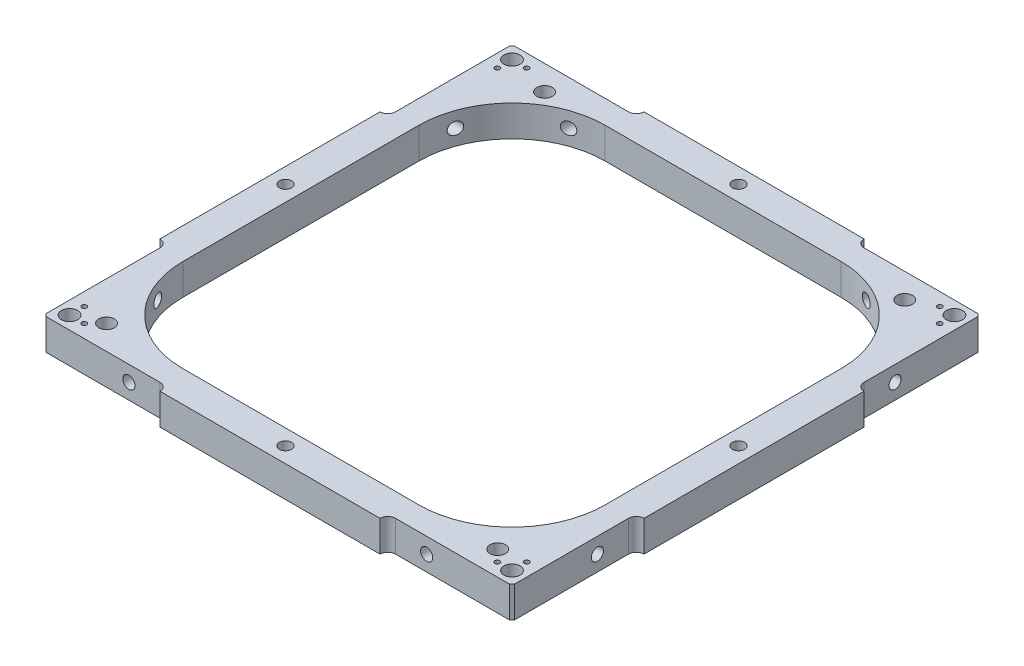
SolidWorks part; units mm, degrees
material "6061-T6 (SS)"
ref_plane "Front Plane" through (0, 0, 0) normal (0, 0, 1) x (1, 0, 0)
ref_plane "Top Plane" through (0, 0, 0) normal (0, 1, 0) x (1, 0, 0)
ref_plane "Right Plane" through (0, 0, 0) normal (1, 0, 0) x (0, 0, -1)
sketch "Sketch1" plane through (0, 0, 0) normal (0, 1, 0) x (1, 0, 0)
  line L0 (-49.5, 22.5125) -> (-47.9125, 22.5125)
  line L1 (-49.5, -49.5) -> (49.5, -49.5)
  line L2 (-49.5, -49.5) -> (-49.5, 49.5)
  line L3 (-49.5, 49.5) -> (49.5, 49.5)
  line L4 (49.5, -49.5) -> (49.5, 49.5)
  line L5 (-49.5, -49.5) -> (49.5, 49.5) construction
  line L6 (-49.5, 49.5) -> (49.5, -49.5) construction
  line L7 (-47.9125, 22.5125) -> (-47.9125, 47.9125)
  line L8 (-47.9125, 47.9125) -> (-22.5125, 47.9125)
  line L9 (-22.5125, 47.9125) -> (-22.5125, 49.5)
  line L10 (22.5125, 49.5) -> (22.5125, 47.9125)
  line L11 (22.5125, 47.9125) -> (47.9125, 47.9125)
  line L12 (47.9125, 47.9125) -> (47.9125, 22.5125)
  line L13 (47.9125, 22.5125) -> (49.5, 22.5125)
  line L14 (49.5, -22.5125) -> (47.9125, -22.5125)
  line L15 (47.9125, -22.5125) -> (47.9125, -47.9125)
  line L16 (47.9125, -47.9125) -> (22.5125, -47.9125)
  line L17 (22.5125, -47.9125) -> (22.5125, -49.5)
  line L18 (-22.5125, -49.5) -> (-22.5125, -47.9125)
  line L19 (-22.5125, -47.9125) -> (-47.9125, -47.9125)
  line L20 (-47.9125, -47.9125) -> (-47.9125, -22.5125)
  line L21 (-47.9125, -22.5125) -> (-49.5, -22.5125)
  point P0 (0, 0)
  dimension "D1" = 99
  dimension "D2" = 99
  dimension "D3" = 26.9875
  dimension "D4" = 1.5875
  dimension "D5" = 26.9875
  dimension "D6" = 1.5875
extrude "Boss-Extrude1" add sketch "Sketch1" along normal blind 6.35 contours L21 L20 L19 L18 L1 L17 L16 L15 L14 L4 L13 L12 L11 L10 L3 L9 L8 L7 L0 L2 region at (0, 0, 0)
chamfer "Chamfer1" distance 0.508 angle 45 4 edges at (47.9125, 3.175, -47.9125) (-47.9125, 3.175, -47.9125) (-47.9125, 3.175, 47.9125) (47.9125, 3.175, 47.9125)
fillet "Fillet1" radius 1.5875 8 edges at (-47.9125, 3.175, -22.5125) (-22.5125, 3.175, -47.9125) (22.5125, 3.175, -47.9125) (47.9125, 3.175, -22.5125) (47.9125, 3.175, 22.5125) (22.5125, 3.175, 47.9125) (-22.5125, 3.175, 47.9125) (-47.9125, 3.175, 22.5125)
hole_wizard "M4x0.7 Tapped Hole2" positions "Sketch2" profile "Sketch3" tap size "M4x0.7" standard "ANSI Metric" end condition through all
sketch "Sketch2" plane through (0, 0, 0) normal (0, -1, 0) x (-1, 0, 0)
  line L0 (-49.5, -22.5125) -> (-49.5, 22.5125) construction
  line L1 (22.5125, 49.5) -> (-22.5125, 49.5) construction
  line L5 (49.5, -22.5125) -> (49.5, 22.5125) construction
  line L6 (22.5125, -49.5) -> (-22.5125, -49.5) construction
  point P0 (-45.25, 45.25)
  point P2 (45.25, 45.25)
  point P4 (45.25, -45.25)
  point P6 (-45.25, -45.25)
  dimension "D1" = 4.25
  dimension "D2" = 4.25
  dimension "D3" = 4.25
  dimension "D4" = 4.25
  dimension "D5" = 4.25
  dimension "D6" = 4.25
  dimension "D7" = 4.25
  dimension "D8" = 4.25
sketch "Sketch3" plane through (45.25, 0, -45.25) normal (1, 0, 0) x (0, 0, -1)
  line L0 (0, 0) -> (0, 6.35)
  line L1 (0, 6.35) -> (1.65, 6.35)
  line L2 (1.65, 6.35) -> (1.65, 0)
  line L5 (1.65, 0) -> (0, 0)
  line L11 (0, -6.35) -> (0, 107.95) construction
  dimension "Thru Tap Drill Dia." = 3.3
  dimension "Thru Tap Drill Depth" = 6.35
cosmetic thread "Hole Thread6" parameters "D2"=4
cosmetic thread "Hole Thread7" parameters "D2"=4
cosmetic thread "Hole Thread8" parameters "D2"=4
cosmetic thread "Hole Thread9" parameters "D2"=4
hole_wizard "M3x0.5 Tapped Hole1" positions "Sketch6" profile "Sketch7" tap size "M3x0.5" standard "ANSI Metric"
sketch "Sketch6" plane through (0, 0, 47.9125) normal (0, 0, 1) x (1, 0, 0)
  line L1 (-24.1, 0) -> (-47.4045, 0) construction
  line L4 (47.4045, 0) -> (24.1, 0) construction
  line L5 (-24.1, 0) -> (-24.1, 6.35) construction
  line L7 (24.1, 6.35) -> (24.1, 0) construction
  point P0 (-30.45, 3.175)
  point P2 (30.45, 3.175)
  dimension "D1" = 6.35
  dimension "D2" = 3.175
  dimension "D3" = 6.35
  dimension "D4" = 3.175
sketch "Sketch7" plane through (-30.45, 3.175, 47.9125) normal (1, 0, 0) x (0, -1, 0)
  line L0 (0, 0) -> (0, 8.3711)
  line L1 (0, 8.3711) -> (1.25, 7.62)
  line L2 (1.25, 7.62) -> (1.25, 0)
  line L5 (1.25, 0) -> (0, 0)
  line L10 (0, 8.3711) -> (-1.25, 7.62) construction
  line L11 (0, -6.35) -> (0, 107.95) construction
  dimension "Tap Drill Dia." = 2.5
  dimension "Tap Drill Depth" = 7.62
  dimension "Drill Angle" = 118
cosmetic thread "Hole Thread1" parameters "D1"=4.7625, "D2"=3
cosmetic thread "Hole Thread2" parameters "D1"=4.7625, "D2"=3
ref_plane "Plane1" through (0, 0, 0) normal (0, 0, 1) x (1, 0, 0)
ref_plane "Plane2" through (0, 0, 0) normal (-1, 0, 0) x (0, 0, 1)
ref_axis "Axis1" through (0, -0.3175, 0) along (0, 1, 0)
pattern_circular "CirPattern1" count 4 over 360 about axis through (0, -0.3175, 0) along (0, 1, 0) of "M3x0.5 Tapped Hole1"
sketch "Sketch9" plane through (0, 6.35, 0) normal (0, 1, 0) x (1, 0, 0)
  line L0 (0, 3.4925) -> (0, -3.4925) construction
  line L1 (-3.4925, 0) -> (3.4925, 0) construction
  circle A0 centre (-40.005, -42.926) radius 1.5875
  circle A1 centre (40.005, -42.926) radius 1.5875
  circle A2 centre (37.465, 42.8625) radius 1.5875
  circle A3 centre (-36.195, 42.8625) radius 1.5875
  dimension "D7" = 3.175
  dimension "D4" = 73.66
  dimension "D1" = 40.005
  dimension "D2" = 40.005
  dimension "D3" = 2.54
  dimension "D5" = 42.8625
  dimension "D6" = 42.926
extrude "Cut-Extrude2" cut sketch "Sketch9" against normal through all
sketch "Sketch11" plane through (0, 6.35, 0) normal (0, 1, 0) x (1, 0, 0)
  line L0 (-22.5125, 49.5) -> (22.5125, 49.5) construction
  line L1 (-43.15, -43.15) -> (43.15, -43.15)
  line L2 (-43.15, -43.15) -> (-43.15, 43.15)
  line L3 (-43.15, 43.15) -> (43.15, 43.15)
  line L4 (43.15, -43.15) -> (43.15, 43.15)
  line L5 (-43.15, -43.15) -> (43.15, 43.15) construction
  line L6 (-43.15, 43.15) -> (43.15, -43.15) construction
  line L7 (49.5, -22.5125) -> (49.5, 22.5125) construction
  line L8 (-44.2725, 42.0275) -> (42.0275, -44.2725)
  line L9 (-42.0275, -44.2725) -> (44.2725, 42.0275)
  line L10 (-42.0275, 44.2725) -> (44.2725, -42.0275)
  line L11 (-44.2725, -42.0275) -> (42.0275, 44.2725)
  circle A5 centre (-36.195, 42.8625) radius 4.7625
  circle A6 centre (-36.195, 42.8625) radius 4.7625
  circle A9 centre (37.465, 42.8625) radius 4.7625
  circle A10 centre (37.465, 42.8625) radius 4.7625
  circle A12 centre (-40.005, -42.926) radius 4.7625
  circle A13 centre (-40.005, -42.926) radius 4.7625
  circle A14 centre (0, 0) radius 25.4
  circle A15 centre (40.005, -42.926) radius 4.7625
  circle A16 centre (40.005, -42.926) radius 4.7625
  circle A17 centre (0, 0) radius 22.225
  point P0 (0, 0)
  dimension "D9" = 50.8
  dimension "D1" = 6.35
  dimension "D2" = 6.35
  dimension "D3" = 3.175
  dimension "D4" = 3.175
  dimension "D5" = 3.175
  dimension "D6" = 3.175
  dimension "D7" = 1.5875
  dimension "D8" = 1.5875
  dimension "D10" = 3.175
hole_wizard "M3x0.5 Tapped Hole3" positions "Sketch14" profile "Sketch15" tap size "M3x0.5" standard "ANSI Metric"
sketch "Sketch14" plane through (0, 6.35, 0) normal (0, 1, 0) x (1, 0, 0)
  line L0 (0, 3.4925) -> (0, -3.4925) construction
  line L1 (-22.5125, -49.5) -> (22.5125, -49.5) construction
  point P0 (0, -46.325)
  dimension "D1" = 3.175
sketch "Sketch15" plane through (0, 6.35, 46.325) normal (1, 0, 0) x (0, 0, 1)
  line L0 (0, 0) -> (0, 8.3711)
  line L1 (0, 8.3711) -> (1.25, 7.62)
  line L2 (1.25, 7.62) -> (1.25, 0)
  line L5 (1.25, 0) -> (0, 0)
  line L10 (0, 8.3711) -> (-1.25, 7.62) construction
  line L11 (0, -6.35) -> (0, 107.95) construction
  dimension "Tap Drill Dia." = 2.5
  dimension "Tap Drill Depth" = 7.62
  dimension "Drill Angle" = 118
cosmetic thread "Hole Thread5" parameters "D1"=6.35, "D2"=4
sketch "Sketch16" plane through (0, 6.35, 0) normal (0, 1, 0) x (1, 0, 0)
  line L0 (-22.5125, 49.5) -> (22.5125, 49.5) construction
  line L1 (-43.15, -43.15) -> (43.15, -43.15)
  line L2 (-43.15, -43.15) -> (-43.15, 43.15)
  line L3 (-43.15, 43.15) -> (43.15, 43.15)
  line L4 (43.15, -43.15) -> (43.15, 43.15)
  line L5 (-43.15, -43.15) -> (43.15, 43.15) construction
  line L6 (-43.15, 43.15) -> (43.15, -43.15) construction
  line L7 (49.5, -22.5125) -> (49.5, 22.5125) construction
  arc A0 (24.1, 43.15) -> (43.15, 24.1) centre (24.1, 24.1) cw
  arc A1 (43.15, -24.1) -> (24.1, -43.15) centre (24.1, -24.1) cw
  arc A2 (-24.1, -43.15) -> (-43.15, -24.1) centre (-24.1, -24.1) cw
  arc A3 (-43.15, 24.1) -> (-24.1, 43.15) centre (-24.1, 24.1) cw
  circle A4 centre (37.465, 42.8625) radius 3.9859 construction
  circle A5 centre (37.465, 42.8625) radius 1.5875 construction
  point P0 (0, 0)
  dimension "D3" = 19.05
  dimension "D1" = 6.35
  dimension "D2" = 6.35
extrude "Cut-Extrude3" cut sketch "Sketch16" against normal through all contours A3 L2 A2 L1 A1 L4 A0 L3 region at (0, 6.35, 0)
pattern_circular "CirPattern2" count 4 over 360 about axis through (0, -0.3175, 0) along (0, 1, 0) of "M3x0.5 Tapped Hole3"
sketch "Sketch17" plane through (0, 6.35, 0) normal (0, 1, 0) x (1, 0, 0)
  circle A0 centre (-36.195, 42.8625) radius 3.25
  circle A1 centre (37.465, 42.8625) radius 3.25
  circle A2 centre (40.005, -42.926) radius 3.25
  circle A3 centre (-40.005, -42.926) radius 3.25
  dimension "D1" = 6.5
  dimension "D2" = 6.5
  dimension "D3" = 6.5
  dimension "D4" = 6.5
sketch "Sketch19" plane through (0, 6.35, 0) normal (0, 1, 0) x (1, 0, 0)
  line L0 (45.25, 45.25) -> (45.25, -45.25) construction
  line L1 (45.25, -45.25) -> (-45.25, -45.25) construction
  line L2 (-45.25, -45.25) -> (-45.25, 45.25) construction
  line L3 (-45.25, 45.25) -> (45.25, 45.25) construction
  circle A0 centre (-42.25, 45.25) radius 0.5
  circle A1 centre (-45.25, 42.25) radius 0.5
  circle A2 centre (42.25, 45.25) radius 0.5
  circle A3 centre (45.25, 42.25) radius 0.5
  circle A4 centre (45.25, -42.25) radius 0.5
  circle A5 centre (42.25, -45.25) radius 0.5
  circle A6 centre (-45.25, -42.25) radius 0.5
  circle A7 centre (-42.25, -45.25) radius 0.5
  circle A8 centre (-45.25, 45.25) radius 3 construction
  circle A9 centre (45.25, 45.25) radius 3 construction
  circle A10 centre (45.25, -45.25) radius 3 construction
  circle A11 centre (-45.25, -45.25) radius 3 construction
  dimension "D1" = 1
  dimension "D2" = 6
extrude "Cut-Extrude4" cut sketch "Sketch19" against normal through all
